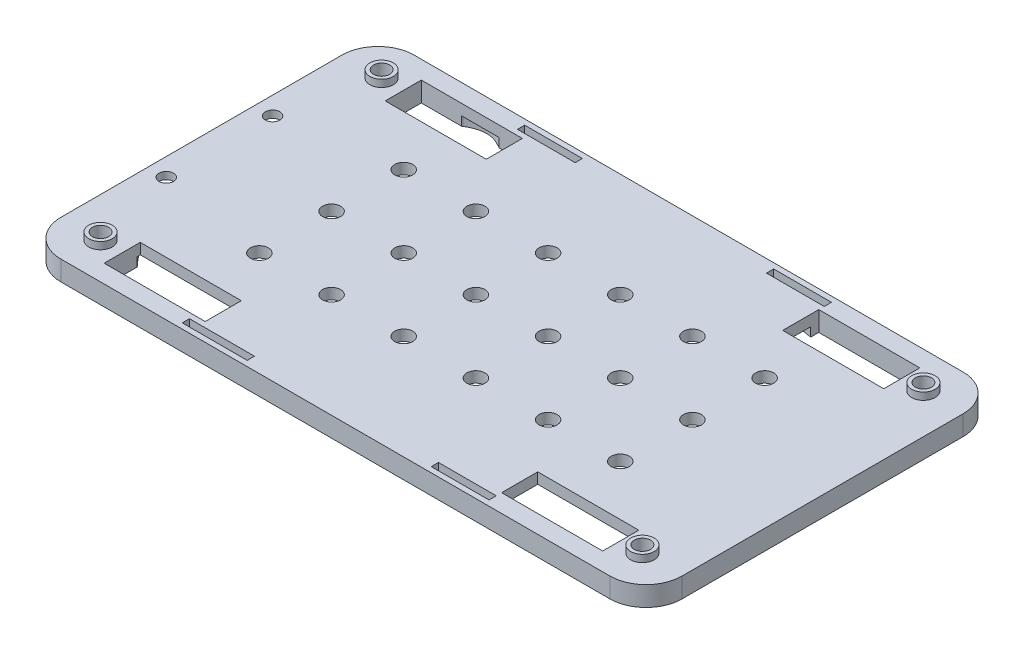
SolidWorks part; units mm, degrees
ref_plane "Front Plane" through (0, 0, 0) normal (0, 0, 1) x (1, 0, 0)
ref_plane "Top Plane" through (0, 0, 0) normal (0, 1, 0) x (1, 0, 0)
ref_plane "Right Plane" through (0, 0, 0) normal (1, 0, 0) x (0, 0, -1)
sketch "Sketch1" plane through (0, 0, 0) normal (0, 1, 0) x (1, 0, 0)
  line L1 (-78.1571, 35.933) -> (-78.1571, -14.1122)
  line L2 (78.9797, 0.0343) -> (-78.1571, 0.0343) construction
  line L3 (-77.1571, 35.7646) -> (-77.1571, -14.1122)
  line L4 (78.9797, -0.9657) -> (-78.1571, -0.9657)
  arc A1 (37.8695, -35.2975) -> (39.5975, -35.2134) centre (38.2635, -25.6055) ccw
  arc A2 (37.9263, -34.299) -> (39.4753, -34.2207) centre (38.2635, -25.6055) ccw
  spline S0 degree 1 poles (-77.1571, -14.1122) (-56.919, -31.9168) knots 0 0 1 1 construction
  spline S1 degree 1 poles (-56.919, -31.9168) (37.9263, -34.299) knots 0 0 1 1 construction
  spline S2 degree 1 poles (39.4753, -34.2207) (77.9849, 0.1477) knots 0 0 1 1 construction
  spline S3 degree 1 poles (77.9849, 0.1477) (25.0602, 52.8732) knots 0 0 1 1 construction
  spline S4 degree 1 poles (25.0602, 52.8732) (-5.6593, 44.1904) knots 0 0 1 1 construction
  spline S5 degree 1 poles (-5.6593, 44.1904) (-43.9853, 50.6886) knots 0 0 1 1 construction
  spline S6 degree 1 poles (-43.9853, 50.6886) (-59.7702, 54.7238) knots 0 0 1 1 construction
  spline S7 degree 1 poles (-59.7702, 54.7238) (-74.5158, 41.0521) knots 0 0 1 1 construction
  spline S8 degree 1 poles (-74.5158, 41.0521) (-77.1571, 35.7646) knots 0 0 1 1 construction
  spline S9 degree 3 poles (-77.1571, -14.1122) (-77.1565, -14.3701) (-77.1092, -14.8732) (-76.8359, -15.9559) (-76.1879, -17.5008) (-75.044, -19.4183) (-73.152, -22.0092) (-70.3495, -25.0822) (-66.8736, -28.0972) (-63.6864, -30.2141) (-61.0019, -31.4062) (-58.8274, -31.848) (-57.5718, -31.8794) (-56.919, -31.9168) knots 0.000484 0.000484 0.000484 0.000484 0.031521 0.062558 0.124632 0.186706 0.248781 0.372929 0.497077 0.621225 0.745373 0.869521 0.993669 0.993669 0.993669 0.993669
  spline S10 degree 3 poles (-56.919, -31.9168) (-56.6769, -31.8873) (-56.2021, -31.8274) (-55.1791, -31.687) (-53.8294, -31.4877) (-52.0759, -31.2184) (-49.5744, -30.8354) (-46.1465, -30.3372) (-41.5825, -29.7813) (-36.5976, -29.3261) (-29.4274, -28.913) (-19.5571, -28.8468) (-6.4839, -29.5875) (5.2448, -30.7865) (15.023, -31.9295) (22.521, -32.809) (30.1538, -33.642) (35.3408, -34.1075) (37.9263, -34.299) knots 0.000538 0.000538 0.000538 0.000538 0.016152 0.031766 0.062993 0.094221 0.125449 0.187904 0.250359 0.312815 0.37527 0.50018 0.625091 0.750001 0.812457 0.874912 0.937367 0.999822 0.999822 0.999822 0.999822
  spline S11 degree 3 poles (39.4753, -34.2207) (41.0079, -34.0574) (44.09, -33.7147) (50.0835, -32.8429) (57.0969, -31.1859) (64.2184, -27.8839) (69.7763, -23.1857) (73.0497, -18.2789) (74.9177, -14.0269) (75.9805, -10.7732) (76.7509, -7.5724) (77.1995, -5.064) (77.4798, -3.2279) (77.6607, -1.9649) (77.8261, -0.8108) (77.9301, -0.1834) (77.9849, 0.1477) knots -0.000309 -0.000309 -0.000309 -0.000309 0.063093 0.126495 0.253299 0.380104 0.506908 0.633712 0.697114 0.760516 0.823918 0.88732 0.919021 0.950722 0.982423 1.014124 1.014124 1.014124 1.014124
  spline S12 degree 3 poles (77.9849, 0.1477) (78.0286, 1.2633) (78.0637, 3.5224) (77.9426, 6.757) (77.6596, 9.9047) (77.0733, 13.9671) (75.9626, 18.7836) (73.4433, 25.9357) (69.0206, 33.8098) (62.0495, 41.4932) (53.7895, 47.3444) (44.6121, 51.2947) (34.9036, 53.2804) (28.3113, 53.2357) (25.0602, 52.8732) knots 0.000169 0.000169 0.000169 0.000169 0.031414 0.062658 0.093902 0.125147 0.187635 0.250124 0.375101 0.500079 0.625056 0.750034 0.875011 0.999988 0.999988 0.999988 0.999988
  spline S13 degree 3 poles (25.0602, 52.8732) (19.8954, 51.6294) (12.3224, 49.1317) (2.1607, 45.9713) (-3.0371, 44.6913) (-5.6593, 44.1904) knots 0.000659 0.000659 0.000659 0.000659 0.498067 0.746772 0.995476 0.995476 0.995476 0.995476
  spline S14 degree 3 poles (-5.6593, 44.1904) (-6.6879, 44.0461) (-8.7287, 43.7719) (-12.9633, 43.2668) (-18.1826, 42.7952) (-23.9015, 42.6322) (-28.8306, 42.9899) (-32.9666, 43.9514) (-35.9177, 45.2914) (-38.1959, 46.6779) (-39.9392, 47.8658) (-41.507, 48.9798) (-42.8638, 49.9292) (-43.6163, 50.4405) (-43.9853, 50.6886) knots -0.000196 -0.000196 -0.000196 -0.000196 0.062587 0.12537 0.250936 0.376501 0.502067 0.627632 0.753198 0.815981 0.878764 0.941546 0.972938 1.004329 1.004329 1.004329 1.004329
  spline S15 degree 3 poles (-43.9853, 50.6886) (-44.2445, 50.8673) (-44.7682, 51.2325) (-45.7507, 51.9331) (-46.8912, 52.7591) (-48.146, 53.6496) (-49.6971, 54.6811) (-51.4608, 55.6487) (-53.4077, 56.2593) (-55.2517, 56.3574) (-56.711, 56.0808) (-57.7948, 55.7138) (-58.5465, 55.3915) (-59.2299, 55.0428) (-59.5837, 54.8359) (-59.7702, 54.7238) knots -0.002497 -0.002497 -0.002497 -0.002497 0.029066 0.060629 0.123754 0.18688 0.250006 0.376257 0.502509 0.62876 0.755012 0.818137 0.881263 0.944389 1.007515 1.007515 1.007515 1.007515
  spline S16 degree 3 poles (-78.1571, -14.1122) (-78.1559, -14.7524) (-77.9173, -15.9777) (-77.0678, -17.9828) (-75.8538, -20.0098) (-73.8827, -22.6985) (-70.9901, -25.8584) (-67.4096, -28.9504) (-64.0991, -31.1349) (-61.2379, -32.3904) (-59.243, -32.7789) (-57.8421, -32.8756) (-57.2118, -32.9007) (-56.8882, -32.9203) knots 0.000409 0.000409 0.000409 0.000409 0.062843 0.125276 0.18771 0.250143 0.375011 0.499878 0.624745 0.749612 0.874479 0.936913 0.999346 0.999346 0.999346 0.999346
  spline S17 degree 3 poles (-56.8882, -32.9203) (-56.6427, -32.8908) (-56.1603, -32.8306) (-55.1309, -32.6904) (-53.7754, -32.491) (-52.0233, -32.2221) (-49.5292, -31.8398) (-46.1189, -31.3427) (-41.5829, -30.7872) (-36.6286, -30.3313) (-29.4997, -29.9158) (-19.6749, -29.8441) (-6.6369, -30.5782) (5.0856, -31.7749) (14.8757, -32.919) (22.3927, -33.8009) (30.0532, -34.6371) (35.2704, -35.1052) (37.8695, -35.2975) knots -0.001373 -0.001373 -0.001373 -0.001373 0.014273 0.029919 0.06121 0.092502 0.123794 0.186377 0.24896 0.311543 0.374127 0.499293 0.62446 0.749626 0.81221 0.874793 0.937376 0.99996 0.99996 0.99996 0.99996
  spline S18 degree 3 poles (39.5975, -35.2134) (41.1398, -35.049) (44.2356, -34.7045) (50.3018, -33.8209) (57.4502, -32.1301) (64.7991, -28.7164) (70.5782, -23.8111) (73.9656, -18.7006) (75.8832, -14.3057) (76.9672, -10.962) (77.7479, -7.6914) (78.1997, -5.145) (78.4804, -3.2966) (78.6613, -2.0308) (78.824, -0.9009) (78.9276, -0.2806) (78.9816, 0.0458) knots -0.000086 -0.000086 -0.000086 -0.000086 0.063428 0.126941 0.253967 0.380993 0.50802 0.635046 0.698559 0.762072 0.825585 0.889098 0.920855 0.952612 0.984368 1.016125 1.016125 1.016125 1.016125
  spline S19 degree 3 poles (78.9816, 0.0458) (79.0271, 1.1797) (79.0647, 3.4739) (78.9444, 6.7697) (78.6587, 9.9749) (78.0642, 14.1169) (76.9341, 19.0326) (74.3646, 26.3398) (69.8439, 34.3944) (62.712, 42.2543) (54.2626, 48.2351) (44.8799, 52.2671) (34.9529, 54.2886) (28.2109, 54.2351) (24.8869, 53.8601) knots -0.000407 -0.000407 -0.000407 -0.000407 0.03088 0.062166 0.093453 0.12474 0.187314 0.249888 0.375035 0.500183 0.62533 0.750478 0.875625 1.000773 1.000773 1.000773 1.000773
  spline S20 degree 3 poles (24.8869, 53.8601) (22.2839, 53.2349) (17.1223, 51.77) (6.9788, 48.4835) (-0.6206, 46.1711) (-5.8226, 45.1772) knots -0.001281 -0.001281 -0.001281 -0.001281 0.247714 0.49671 0.9947 0.9947 0.9947 0.9947
  spline S21 degree 3 poles (-5.8226, 45.1772) (-6.8463, 45.0337) (-8.8779, 44.761) (-13.0882, 44.2593) (-18.2643, 43.7927) (-23.9018, 43.6338) (-28.7026, 43.9859) (-32.6523, 44.9085) (-35.4477, 46.177) (-37.6484, 47.5152) (-39.3619, 48.6824) (-40.9248, 49.793) (-42.292, 50.7496) (-43.0505, 51.2651) (-43.4225, 51.5151) knots 0.000305 0.000305 0.000305 0.000305 0.063048 0.125791 0.251276 0.376761 0.502247 0.627732 0.753218 0.815961 0.878703 0.941446 0.972817 1.004189 1.004189 1.004189 1.004189
  spline S22 degree 3 poles (-43.4225, 51.5151) (-43.6786, 51.6918) (-44.1958, 52.0526) (-45.1684, 52.7462) (-46.308, 53.5714) (-47.577, 54.4721) (-49.1727, 55.5335) (-51.0441, 56.5648) (-53.2147, 57.2519) (-55.3195, 57.3652) (-56.9568, 57.0533) (-58.1477, 56.6506) (-58.9689, 56.2985) (-59.5708, 55.992) (-60.0059, 55.7483) (-60.1862, 55.6406) (-60.2803, 55.5839) knots -0.002294 -0.002294 -0.002294 -0.002294 0.029245 0.060783 0.12386 0.186936 0.250013 0.376167 0.50232 0.628473 0.754627 0.817704 0.88078 0.943857 0.975396 1.006934 1.006934 1.006934 1.006934
  spline S23 degree 3 poles (-60.2803, 55.5839) (-60.715, 55.3297) (-61.582, 54.801) (-63.2222, 53.7187) (-65.9105, 51.7373) (-69.2431, 48.741) (-72.0244, 45.6929) (-73.7392, 43.6279) (-74.6657, 42.4756) (-75.1049, 41.9202) (-75.3265, 41.639) knots 0.000427 0.000427 0.000427 0.000427 0.063268 0.126109 0.251792 0.503158 0.754524 0.880206 0.943048 1.005889 1.005889 1.005889 1.005889
  spline S24 degree 3 poles (-59.7702, 54.7238) (-60.1936, 54.4761) (-61.0386, 53.9612) (-62.6368, 52.9072) (-65.2587, 50.9763) (-68.5171, 48.0498) (-71.2443, 45.0657) (-73.1899, 42.7247) (-74.0698, 41.6179) (-74.5158, 41.0521) knots 0.000174 0.000174 0.000174 0.000174 0.062881 0.125589 0.251004 0.501833 0.752662 0.878077 1.003492 1.003492 1.003492 1.003492
  spline S25 degree 3 poles (-74.5158, 41.0521) (-75.0658, 40.2217) (-76.0765, 38.4779) (-76.8336, 36.6875) (-77.1571, 35.7646) knots 0.499549 0.499549 0.499549 0.499549 0.499766 0.499983 0.499983 0.499983 0.499983
  spline S26 degree 3 poles (-75.3265, 41.639) (-75.92, 40.746) (-77.0064, 38.8701) (-77.815, 36.9314) (-78.1571, 35.933) knots 0.499546 0.499546 0.499546 0.499546 0.49977 0.499995 0.499995 0.499995 0.499995
  point P0 (0.4631, 0.0343)
  dimension "D1" = 1
sketch "Sketch6" plane through (0, 0, 0) normal (0, 1, 0) x (1, 0, 0)
  line L0 (-78.1571, 35.933) -> (-78.1571, -14.1122) construction
  line L1 (73.9816, 59.5839) -> (-78.1571, 59.5839)
  line L2 (83.9816, 49.5839) -> (83.9816, -28.2975)
  line L3 (73.9816, -38.2975) -> (-78.1571, -38.2975)
  line L4 (-88.1571, 49.5839) -> (-88.1571, -28.2975)
  arc A0 (-78.1571, -38.2975) -> (-88.1571, -28.2975) centre (-78.1571, -28.2975) cw
  arc A1 (-88.1571, 49.5839) -> (-78.1571, 59.5839) centre (-78.1571, 49.5839) cw
  arc A2 (73.9816, 59.5839) -> (83.9816, 49.5839) centre (73.9816, 49.5839) cw
  arc A3 (83.9816, -28.2975) -> (73.9816, -38.2975) centre (73.9816, -28.2975) cw
  dimension "D5" = 10
  dimension "D1" = 5
  dimension "D2" = 10
  dimension "D3" = 3
  dimension "D4" = 4
extrude "Boss-Extrude2" add sketch "Sketch6" along normal blind 6.5
extrude "Cut-Extrude1" cut sketch "Sketch1" along normal blind 2.5 contours A2 S11 L4 L3 S9 S10 | S24 S25 L3 L4 S11 S12 S13 S14 S15 region at (0.1139, 0, 15.5782) region at (-2.2602, 0, -23.2786)
sketch "Sketch7" plane through (0, 0, 0) normal (0, -1, 0) x (1, 0, 0)
  line L1 (-76.2189, 14.1122) -> (-91.3452, 14.1122)
  line L2 (-76.2189, 14.1122) -> (-76.2189, -35.933)
  line L3 (-76.2189, -35.933) -> (-91.3452, -35.933)
  line L4 (-91.3452, 14.1122) -> (-91.3452, -35.933)
extrude "Cut-Extrude2" cut sketch "Sketch7" against normal up to surface (2.5 mm away) contours L2 L1 L4 L3 up to face at (-19.4492, 2.5, -12.7234)
sketch "Sketch8" plane through (0, 6.5, 0) normal (0, 1, 0) x (1, 0, 0)
  line L0 (83.9816, 10.6432) -> (-88.1571, 10.6432) construction
  line L1 (83.9816, -28.2975) -> (83.9816, 49.5839) construction
  line L2 (-88.1571, 49.5839) -> (-88.1571, -28.2975) construction
  line L3 (-2.0877, 59.5839) -> (-2.0877, -38.2975) construction
  line L4 (73.9816, 59.5839) -> (-78.1571, 59.5839) construction
  line L5 (-78.1571, -38.2975) -> (73.9816, -38.2975) construction
  line L7 (78.9816, 54.5839) -> (38.9816, 54.5839)
  line L8 (78.9816, 54.5839) -> (78.9816, 44.5839)
  line L9 (78.9816, 44.5839) -> (38.9816, 44.5839)
  line L10 (38.9816, 54.5839) -> (38.9816, 44.5839)
  line L22 (38.9816, 49.5839) -> (78.9816, 49.5839) construction
  line L23 (66.9816, 54.5839) -> (66.9816, 44.5839)
  circle A1 centre (72.9816, 49.5839) radius 3.5
  dimension "D6" = 7
  dimension "D1" = 10
  dimension "D2" = 40
  dimension "D3" = 5
  dimension "D4" = 5
  dimension "D5" = 6
  dimension "D7" = 6
sketch "Sketch9" plane through (0, 0, 0) normal (0, -1, 0) x (1, 0, 0)
  circle A0 centre (72.9816, -49.5839) radius 4.5
  dimension "D1" = 9
extrude "Cut-Extrude5" cut sketch "Sketch9" against normal blind 1
sketch "Sketch10" plane through (0, 1, 0) normal (0, -1, 0) x (1, 0, 0)
  circle A0 centre (72.9816, -49.5839) radius 2.25
  dimension "D1" = 4.5
extrude "Cut-Extrude6" cut sketch "Sketch10" against normal blind 21
extrude "Cut-Extrude8" cut sketch "Sketch8" against normal blind 42 contours L23 L7 L10 L9 region at (52.9816, 6.5, -49.5839)
extrude "Cut-Extrude9" cut sketch "Sketch8<3>" against normal blind 1 contours L7 L23 L9 L8 A1 region at (78.8254, 6.5, -49.5839)
sketch "Sketch8<3>" plane through (0, 6.5, 0) normal (0, 1, 0) x (1, 0, 0) same geometry as "Sketch8"
sketch "Sketch12" plane through (0, 6.5, 0) normal (0, 1, 0) x (1, 0, 0)
  line L0 (-88.1571, 10.6432) -> (83.9816, 10.6432) construction
  line L1 (-88.1571, 49.5839) -> (-88.1571, -28.2975) construction
  line L2 (83.9816, -28.2975) -> (83.9816, 49.5839) construction
  line L3 (-2.0877, 59.5839) -> (-2.0877, -36.8461) construction
  line L4 (73.9816, 59.5839) -> (-78.1571, 59.5839) construction
ref_plane "Plane1" through (0, 0, -10.6432) normal (0, 0, 1) x (1, 0, 0)
ref_plane "Plane2" through (-2.0877, 0, 0) normal (-1, 0, 0) x (0, 0, 1)
mirror "Mirror1" about plane through (0, 0, -10.6432) normal (0, 0, 1) of "Cut-Extrude5", "Cut-Extrude6", "Cut-Extrude8", "Cut-Extrude9"
mirror "Mirror2" about plane through (-2.0877, 0, 0) normal (-1, 0, 0) of "Mirror1", "Cut-Extrude9", "Cut-Extrude8", "Cut-Extrude6", "Cut-Extrude5"
sketch "Sketch13" plane through (0, 6.5, 0) normal (0, 1, 0) x (1, 0, 0)
  line L0 (-83.1571, 44.5839) -> (-43.1571, 44.5839) construction
  line L1 (58.9816, 39.5839) -> (-63.1571, 39.5839)
  line L2 (58.9816, 39.5839) -> (58.9816, -18.2975)
  line L3 (58.9816, -18.2975) -> (-63.1571, -18.2975)
  line L4 (-63.1571, 39.5839) -> (-63.1571, -18.2975)
  line L5 (58.9816, 39.5839) -> (-63.1571, -18.2975) construction
  line L6 (58.9816, -18.2975) -> (-63.1571, 39.5839) construction
  line L7 (-83.1571, -23.2975) -> (-43.1571, -23.2975) construction
  line L8 (83.9816, -28.2975) -> (83.9816, 49.5839) construction
  line L9 (-88.1571, 49.5839) -> (-88.1571, -28.2975) construction
  point P0 (-2.0877, 10.6432)
  dimension "D1" = 5
  dimension "D2" = 5
  dimension "D3" = 25
  dimension "D4" = 25
extrude "Cut-Extrude10" cut sketch "Sketch13" against normal blind 1
sketch "Sketch14" plane through (0, 5.5, 0) normal (0, 1, 0) x (1, 0, 0)
  line L0 (-63.1571, 10.6432) -> (58.9816, 10.6432) construction
  line L1 (-63.1571, 39.5839) -> (-63.1571, -18.2975) construction
  line L2 (58.9816, -18.2975) -> (58.9816, 39.5839) construction
  line L3 (-63.1571, -9.3568) -> (58.9816, -9.3568) construction
  line L4 (-63.1571, 10.6432) -> (58.9816, 10.6432) construction
  line L5 (-63.1571, 30.6432) -> (58.9816, 30.6432) construction
  circle A1 centre (-12.0877, 10.6432) radius 2.5
  circle A2 centre (-32.0877, 10.6432) radius 2.5
  circle A3 centre (-52.0877, 10.6432) radius 2.5
  circle A4 centre (-12.0877, 10.6432) radius 2.5
  circle A5 centre (-32.0877, 10.6432) radius 2.5
  circle A6 centre (7.9123, 10.6432) radius 2.5
  circle A7 centre (-12.0877, 10.6432) radius 2.5
  circle A8 centre (27.9123, 10.6432) radius 2.5
  circle A9 centre (7.9123, 10.6432) radius 2.5
  circle A10 centre (7.9123, 10.6432) radius 2.5
  circle A11 centre (27.9123, 10.6432) radius 2.5
  circle A12 centre (47.9123, 10.6432) radius 2.5
  circle A13 centre (-12.0877, -9.3568) radius 2.5
  circle A14 centre (-32.0877, -9.3568) radius 2.5
  circle A15 centre (-52.0877, -9.3568) radius 2.5
  circle A16 centre (-12.0877, -9.3568) radius 2.5
  circle A17 centre (-32.0877, -9.3568) radius 2.5
  circle A18 centre (7.9123, -9.3568) radius 2.5
  circle A19 centre (-12.0877, -9.3568) radius 2.5
  circle A20 centre (27.9123, -9.3568) radius 2.5
  circle A21 centre (7.9123, -9.3568) radius 2.5
  circle A22 centre (7.9123, -9.3568) radius 2.5
  circle A23 centre (27.9123, -9.3568) radius 2.5
  circle A24 centre (47.9123, -9.3568) radius 2.5
  circle A25 centre (-12.0877, 10.6432) radius 2.5
  circle A26 centre (-32.0877, 10.6432) radius 2.5
  circle A27 centre (-52.0877, 10.6432) radius 2.5
  circle A28 centre (-12.0877, 10.6432) radius 2.5
  circle A29 centre (-32.0877, 10.6432) radius 2.5
  circle A30 centre (7.9123, 10.6432) radius 2.5
  circle A31 centre (-12.0877, 10.6432) radius 2.5
  circle A32 centre (27.9123, 10.6432) radius 2.5
  circle A33 centre (7.9123, 10.6432) radius 2.5
  circle A34 centre (7.9123, 10.6432) radius 2.5
  circle A35 centre (27.9123, 10.6432) radius 2.5
  circle A36 centre (47.9123, 10.6432) radius 2.5
  circle A37 centre (-12.0877, 30.6432) radius 2.5
  circle A38 centre (-32.0877, 30.6432) radius 2.5
  circle A39 centre (-52.0877, 30.6432) radius 2.5
  circle A40 centre (-12.0877, 30.6432) radius 2.5
  circle A41 centre (-32.0877, 30.6432) radius 2.5
  circle A42 centre (7.9123, 30.6432) radius 2.5
  circle A43 centre (-12.0877, 30.6432) radius 2.5
  circle A44 centre (27.9123, 30.6432) radius 2.5
  circle A45 centre (7.9123, 30.6432) radius 2.5
  circle A46 centre (7.9123, 30.6432) radius 2.5
  circle A47 centre (27.9123, 30.6432) radius 2.5
  circle A48 centre (47.9123, 30.6432) radius 2.5
  point P8 (-2.0877, 10.6432)
  point P37 (-2.0877, -9.3568)
  point P64 (-2.0877, 10.6432)
  point P91 (-2.0877, 30.6432)
  dimension "D2" = 5
  dimension "D1" = 10
  dimension "D3" = 3
  dimension "D4" = 4
  dimension "D5" = 2
  dimension "D6" = 2
extrude "Cut-Extrude11" cut sketch "Sketch14" against normal blind 57 contours A39 | A42 | A44 | A48 | A12 | A6 | A1 | A2 | A3 | A24 | A20 | A18 | A13 | A14 | A15 | A38 | A37 | A8 region at (-12.0877, 5.5, -10.6432) region at (-32.0877, 5.5, -10.6432) region at (-52.0877, 5.5, -10.6432) region at (7.9123, 5.5, -10.6432) region at (47.9123, 5.5, -10.6432) region at (-12.0877, 5.5, 9.3568) region at (-32.0877, 5.5, 9.3568) region at (-52.0877, 5.5, 9.3568) region at (7.9123, 5.5, 9.3568) region at (27.9123, 5.5, 9.3568) region at (47.9123, 5.5, 9.3568) region at (-52.0877, 5.5, -30.6432) region at (7.9123, 5.5, -30.6432) region at (27.9123, 5.5, -30.6432) region at (47.9123, 5.5, -30.6432)
sketch "Sketch16" plane through (0, 0, 0) normal (0, -1, 0) x (1, 0, 0)
  line L0 (78.9816, -0.5458) -> (78.9816, -79.1994) construction
  line L1 (22.9816, -56.0839) -> (-37.6427, -56.0839) construction
  line L2 (73.9816, -59.5839) -> (-78.1571, -59.5839) construction
  line L3 (38.9816, -54.3238) -> (38.9816, 38.2975) construction
  line L4 (38.9816, -59.5839) -> (38.9816, -54.3238) construction
  line L5 (38.9816, -56.0839) -> (22.9816, -56.0839)
  line L6 (38.9816, -56.0839) -> (38.9816, -58.0839)
  line L7 (38.9816, -58.0839) -> (22.9816, -58.0839)
  line L8 (22.9816, -56.0839) -> (22.9816, -58.0839)
  line L9 (-78.1571, 38.2975) -> (73.9816, 38.2975) construction
  line L10 (22.9816, -56.0839) -> (22.9816, 38.2975) construction
  line L12 (38.9816, 36.7975) -> (22.9816, 36.7975)
  line L13 (38.9816, 36.7975) -> (38.9816, 34.7975)
  line L14 (38.9816, 34.7975) -> (22.9816, 34.7975)
  line L15 (22.9816, 36.7975) -> (22.9816, 34.7975)
  line L16 (22.9816, 34.7975) -> (-46.0184, 34.7975) construction
  line L17 (-30.0184, -56.0839) -> (-46.0184, -56.0839)
  line L18 (-30.0184, -56.0839) -> (-30.0184, -58.0839)
  line L19 (-30.0184, -58.0839) -> (-46.0184, -58.0839)
  line L20 (-46.0184, -56.0839) -> (-46.0184, -58.0839)
  line L22 (-28.0184, 34.7975) -> (-46.0184, 34.7975)
  line L23 (-28.0184, 34.7975) -> (-28.0184, 36.7975)
  line L24 (-28.0184, 36.7975) -> (-46.0184, 36.7975)
  line L25 (-46.0184, 34.7975) -> (-46.0184, 36.7975)
  dimension "D1" = 40
  dimension "D2" = 16
  dimension "D3" = 1.5
  dimension "D4" = 2
  dimension "D5" = 2
  dimension "D6" = 1.5
  dimension "D7" = 125
  dimension "D8" = 16
  dimension "D9" = 2
  dimension "D10" = 18
  dimension "D11" = 2
extrude "Cut-Extrude12" cut sketch "Sketch16" against normal blind 57
sketch "Sketch17" plane through (0, 5.5, 0) normal (0, 1, 0) x (1, 0, 0)
  line L1 (-99.5963, 69.0247) -> (98.4238, 69.0247)
  line L2 (-99.5963, 69.0247) -> (-99.5963, -53.2143)
  line L3 (-99.5963, -53.2143) -> (98.4238, -53.2143)
  line L4 (98.4238, 69.0247) -> (98.4238, -53.2143)
extrude "Cut-Extrude14" cut sketch "Sketch17" along normal blind 48.5
sketch "Sketch23" plane through (0, 2.5, 0) normal (0, -1, 0) x (1, 0, 0)
  line L0 (-88.1571, -10.9104) -> (-64.7808, -10.9104) construction
  line L1 (-88.1571, -35.933) -> (-88.1571, 14.1122) construction
  circle A0 centre (-83.1571, 4.0896) radius 2
  circle A1 centre (-83.1571, 4.0896) radius 4.25
  dimension "D1" = 4
  dimension "D4" = 8.5
  dimension "D2" = 15
  dimension "D3" = 5
extrude "Cut-Extrude15" cut sketch "Sketch23" against normal blind 48.5 contours A0
extrude "Cut-Extrude16" cut sketch "Sketch23<3>" against normal blind 1
sketch "Sketch23<3>" plane through (0, 2.5, 0) normal (0, -1, 0) x (1, 0, 0) same geometry as "Sketch23"
mirror "Mirror4" about plane through (0, 0, -10.6432) normal (0, 0, 1) of "Cut-Extrude16", "Cut-Extrude15"
sketch "Sketch24" plane through (0, 5.5, 0) normal (0, 1, 0) x (1, 0, 0)
  circle A0 centre (-77.1571, 49.5839) radius 3.25
  circle A1 centre (-77.1571, 49.5839) radius 2.25
  circle A2 centre (72.9816, 49.5839) radius 2.25
  circle A3 centre (72.9816, 49.5839) radius 3.25
  circle A4 centre (72.9816, -28.2975) radius 2.25
  circle A5 centre (-77.1571, -28.2975) radius 2.25
  circle A6 centre (-77.1571, -28.2975) radius 3.25
  circle A7 centre (72.9816, -28.2975) radius 3.25
  dimension "D1" = 6.5
  dimension "D2" = 6.5
  dimension "D3" = 6.5
  dimension "D4" = 6.5
extrude "Boss-Extrude3" add sketch "Sketch24" along normal blind 2
